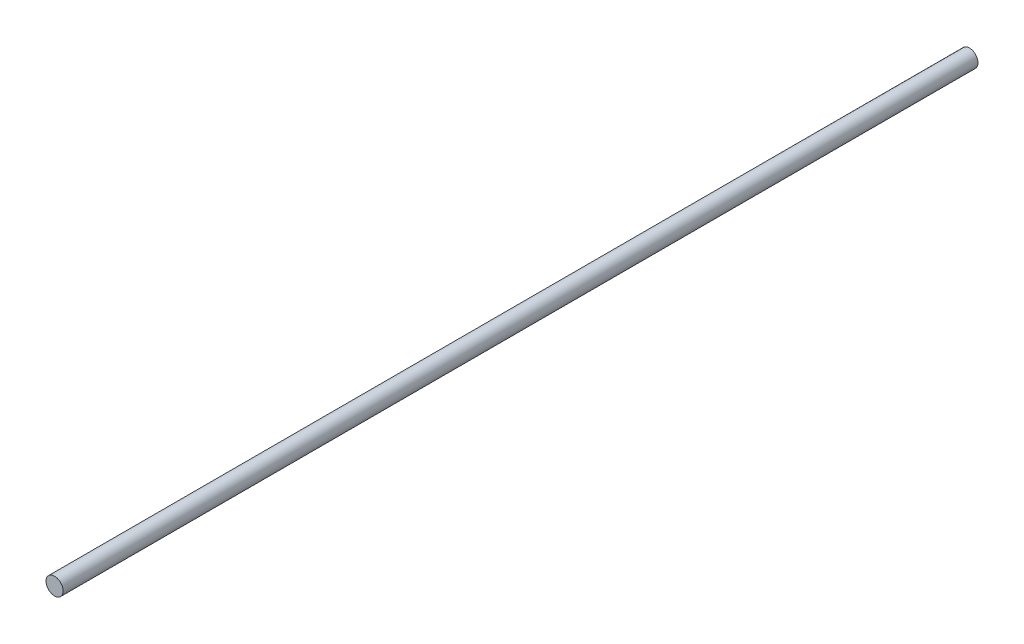
SolidWorks part; units mm, degrees
ref_plane "Plan de face" through (0, 0, 0) normal (0, 0, 1) x (1, 0, 0)
ref_plane "Plan de dessus" through (0, 0, 0) normal (0, 1, 0) x (1, 0, 0)
ref_plane "Plan de droite" through (0, 0, 0) normal (1, 0, 0) x (0, 0, -1)
sketch "Esquisse1" plane through (0, 0, 0) normal (0, 0, 1) x (1, 0, 0)
  circle A0 centre (0, 0) radius 1.5
  dimension "D1" = 3
extrude "Boss.-Extru.1" add sketch "Esquisse1" along normal blind 160
